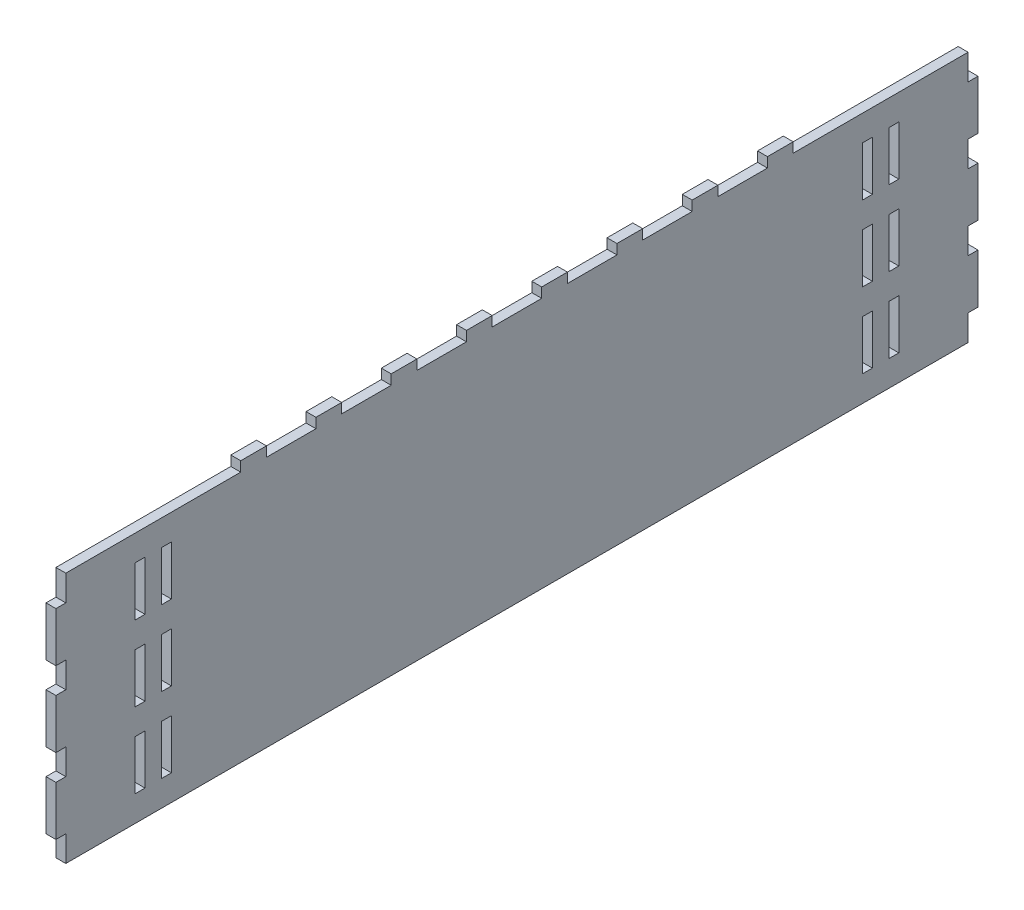
SolidWorks part; units mm, degrees
material "ENPH 253 Hardboard"
ref_plane "Front Plane" through (0, 0, 0) normal (0, 0, 1) x (1, 0, 0)
ref_plane "Top Plane" through (0, 0, 0) normal (0, 1, 0) x (1, 0, 0)
ref_plane "Right Plane" through (0, 0, 0) normal (1, 0, 0) x (0, 0, -1)
sketch "Sketch1" plane through (0, 0, 0) normal (1, 0, 0) x (0, 0, -1)
  line L1 (-139.7, 38.1) -> (139.7, 38.1)
  line L2 (-139.7, 38.1) -> (-139.7, -38.1)
  line L3 (-139.7, -38.1) -> (139.7, -38.1)
  line L4 (139.7, 38.1) -> (139.7, -38.1)
  line L5 (-139.7, 38.1) -> (139.7, -38.1) construction
  line L6 (-139.7, -38.1) -> (139.7, 38.1) construction
  point P0 (0, 0)
  dimension "D1" = 279.4
  dimension "D2" = 76.2
extrude "Boss-Extrude1" add sketch "Sketch1" against normal blind 3 contours L2 L3 L4 L1
sketch "Sketch3" plane through (-3, 0, 0) normal (-1, 0, 0) x (0, 0, 1)
  line L2 (-139.7, 38.1) -> (-139.7, -38.1) construction
  line L7 (-112.7, 30.3) -> (-115.7, 30.3)
  line L8 (-112.7, 30.3) -> (-112.7, 15.3)
  line L9 (-139.7, 38.1) -> (-136.7, 38.1)
  line L10 (-139.7, 38.1) -> (-139.7, 30.3)
  line L11 (-139.7, 30.3) -> (-136.7, 30.3)
  line L12 (-136.7, 38.1) -> (-136.7, 30.3)
  line L13 (-112.7, 15.3) -> (-115.7, 15.3)
  line L14 (-115.7, 30.3) -> (-115.7, 15.3)
  line L15 (139.7, 38.1) -> (-139.7, 38.1) construction
  dimension "D5" = 15
  dimension "D6" = 3
  dimension "D7" = 24
  dimension "D8" = 7.8
  dimension "D9" = 7.8
  dimension "D10" = 3
extrude "Cut-Extrude1" cut sketch "Sketch3" against normal through all
pattern_linear "LPattern1" count 4 spacing 22.8 along (0, -1, 0) of "Cut-Extrude1"
mirror "Mirror1" about plane through (0, 0, 0) normal (0, 0, 1) of "LPattern1"
sketch "Sketch4" plane through (0, 0, 0) normal (1, 0, 0) x (0, 0, -1)
  line L0 (-112.7, 15.3) -> (-112.7, 30.3) construction
  line L1 (-107.7, 30.3) -> (-104.7, 30.3)
  line L2 (-107.7, 30.3) -> (-107.7, 15.3)
  line L3 (-107.7, 15.3) -> (-104.7, 15.3)
  line L4 (-104.7, 30.3) -> (-104.7, 15.3)
  line L5 (-136.7, 38.1) -> (136.7, 38.1) construction
  dimension "D1" = 5
  dimension "D2" = 3
  dimension "D3" = 7.8
  dimension "D4" = 15
extrude "Cut-Extrude2" cut sketch "Sketch4" against normal blind 10
pattern_linear "LPattern2" count 3 spacing 22.8 along (0, -1, 0) of "Cut-Extrude2"
mirror "Mirror2" about plane through (0, 0, 0) normal (0, 0, 1) of "LPattern2"
sketch "Sketch5" plane through (0, 38.1, 0) normal (0, 1, 0) x (1, 0, 0)
  line L0 (-3, -136.7) -> (-3, 136.7) construction
  line L1 (-3, -75.9) -> (0, -75.9)
  line L2 (-3, -75.9) -> (-3, -83.7)
  line L3 (-3, -83.7) -> (0, -83.7)
  line L4 (0, -75.9) -> (0, -83.7)
  line L5 (0, -136.7) -> (-3, -136.7) construction
  dimension "D1" = 53
  dimension "D2" = 7.8
  dimension "D3" = 3
extrude "Boss-Extrude2" add sketch "Sketch5" along normal blind 3
pattern_linear "LPattern3" count 8 spacing 22.8 along (0, 0, -1) of "Boss-Extrude2"
